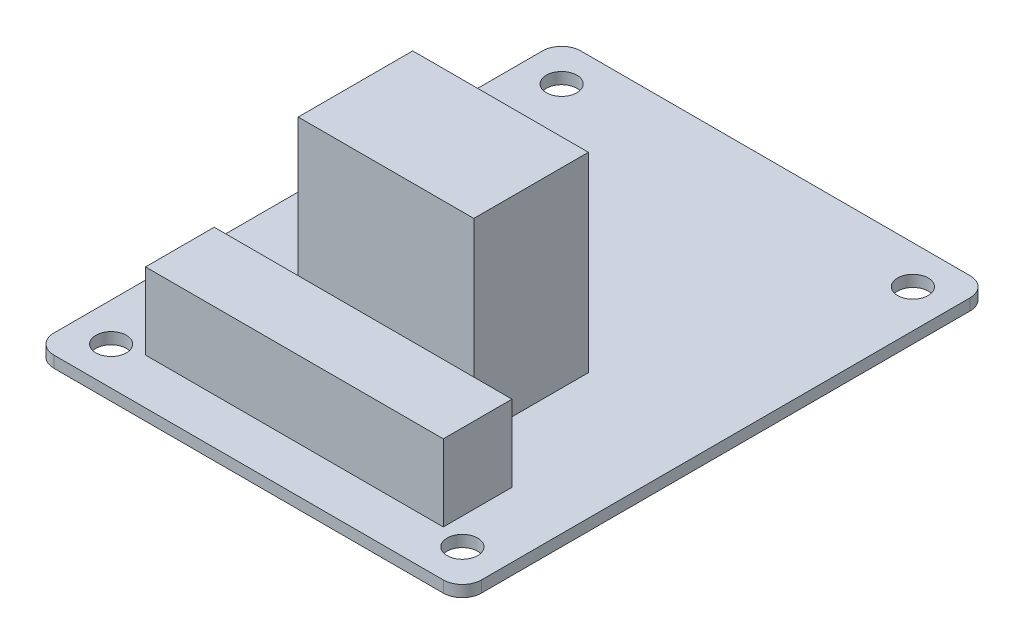
SolidWorks part; units mm, degrees
ref_plane "Front Plane" through (0, 0, 0) normal (0, 0, 1) x (1, 0, 0)
ref_plane "Top Plane" through (0, 0, 0) normal (0, 1, 0) x (1, 0, 0)
ref_plane "Right Plane" through (0, 0, 0) normal (1, 0, 0) x (0, 0, -1)
sketch "Sketch1" plane through (0, 0, 0) normal (0, 1, 0) x (1, 0, 0)
  line L0 (28, 0) -> (28, 69) construction
  line L1 (2.5, 0) -> (53.5, 0)
  line L2 (0, 2.5) -> (0, 66.5)
  line L3 (2.5, 69) -> (53.5, 69)
  line L4 (56, 2.5) -> (56, 66.5)
  line L5 (8.5, 15) -> (47.5, 15)
  line L6 (8.5, 15) -> (8.5, 6)
  line L7 (8.5, 6) -> (47.5, 6)
  line L8 (47.5, 15) -> (47.5, 6)
  line L9 (0, 34.5) -> (56, 34.5) construction
  line L11 (16.5, 18) -> (39.5, 18)
  line L12 (16.5, 18) -> (16.5, 33)
  line L13 (16.5, 33) -> (39.5, 33)
  line L14 (39.5, 18) -> (39.5, 33)
  line L15 (16.5, 18) -> (39.5, 33) construction
  line L16 (16.5, 33) -> (39.5, 18) construction
  circle A0 centre (5, 5) radius 2
  circle A1 centre (51, 5) radius 2
  circle A2 centre (51, 64) radius 2
  circle A3 centre (5, 64) radius 2
  arc A4 (53.5, 69) -> (56, 66.5) centre (53.5, 66.5) cw
  arc A5 (53.5, 0) -> (56, 2.5) centre (53.5, 2.5) ccw
  arc A6 (2.5, 0) -> (0, 2.5) centre (2.5, 2.5) cw
  arc A7 (0, 66.5) -> (2.5, 69) centre (2.5, 66.5) cw
  point P21 (28, 26.7019)
  point P22 (28, 6)
  point P23 (28, 25.5)
  point P30 (56, 69)
  point P33 (56, 0)
  point P36 (0, 0)
  dimension "D3" = 4
  dimension "D12" = 2.5
  dimension "D1" = 56
  dimension "D2" = 69
  dimension "D4" = 5
  dimension "D5" = 5
  dimension "D6" = 9
  dimension "D7" = 39
  dimension "D8" = 6
  dimension "D9" = 15
  dimension "D10" = 23
  dimension "D11" = 3
extrude "Boss-Extrude1" add sketch "Sketch1" along normal blind 1.5 contours A7 L2 A6 L1 A5 L4 A4 L3 A1 A0 L14 L11 L12 L13 L5 L8 L7 L6 A2 A3 | L11 L14 L13 L12 | L8 L5 L6 L7 region at (28, 0, -38.2043) region at (28, 0, -10.5) region at (28, 0, -25.5)
extrude "Boss-Extrude2" add sketch "Sketch1<4>" along normal blind 10 from surface separate body contours L8 L5 L6 L7 region at (28, 0, -10.5) starting at face at (28, 1.5, -34.5)
sketch "Sketch1<4>" plane through (0, 0, 0) normal (0, 1, 0) x (1, 0, 0) same geometry as "Sketch1"
extrude "Boss-Extrude3" add sketch "Sketch1<5>" along normal blind 25 from surface separate body contours L11 L14 L13 L12 region at (28, 0, -25.5) starting at face at (28, 1.5, -34.5)
sketch "Sketch1<5>" plane through (0, 0, 0) normal (0, 1, 0) x (1, 0, 0) same geometry as "Sketch1"
